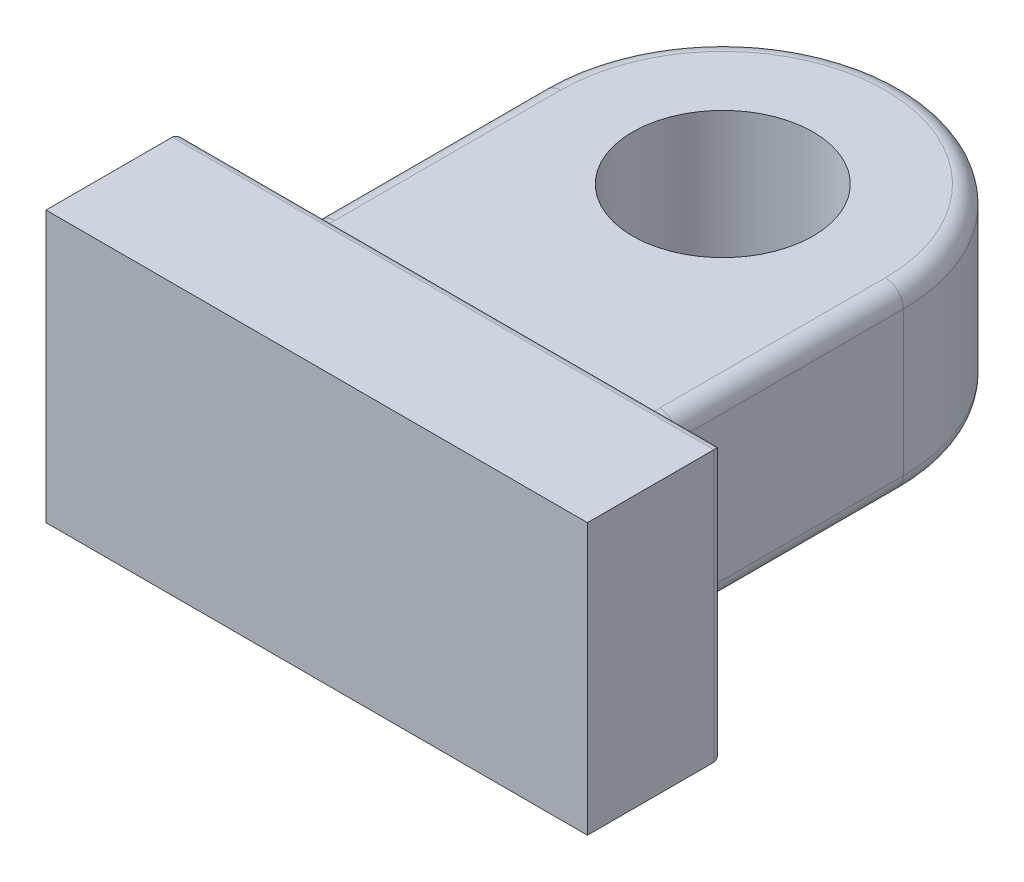
SolidWorks part; units mm, degrees
ref_plane "Front Plane" through (0, 0, 0) normal (0, 0, 1) x (1, 0, 0)
ref_plane "Top Plane" through (0, 0, 0) normal (0, 1, 0) x (1, 0, 0)
ref_plane "Right Plane" through (0, 0, 0) normal (1, 0, 0) x (0, 0, -1)
sketch "Sketch2" plane through (0, 0, 0) normal (0, 0, 1) x (1, 0, 0)
  line L1 (0, 0) -> (60, 0)
  line L2 (0, 0) -> (0, -30)
  line L3 (0, -30) -> (60, -30)
  line L4 (60, 0) -> (60, -30)
  dimension "D1" = 60
  dimension "D2" = 30
extrude "Boss-Extrude1" add sketch "Sketch2" along normal blind 15
ref_plane "Plane1" through (0, -15, 0) normal (0, 1, 0) x (1, 0, 0)
sketch "Sketch4" plane through (0, -15, 0) normal (0, 1, 0) x (1, 0, 0)
  line L0 (10, 30) -> (10, 0)
  line L1 (60, 0) -> (0, 0) construction
  line L2 (50, 30) -> (50, 0)
  line L3 (10, 0) -> (50, 0)
  circle A0 centre (30, 30) radius 10
  arc A1 (50, 30) -> (10, 30) centre (30, 30) ccw
  dimension "D1" = 20
  dimension "D2" = 20
  dimension "D3" = 30
  dimension "D4" = 10
extrude "Boss-Extrude2" add sketch "Sketch4" along normal mid plane 20
fillet "Fillet1" radius 5 2 edges at (10, -15, 0) (50, -15, 0)
fillet "Fillet2" radius 2 10 edges at (51.4645, -25, -1.4645) (50, -25, -17.5) (30, -25, -50) (8.5355, -25, -1.4645) (51.4645, -5, -1.4645) (50, -5, -17.5) (30, -5, -50) (8.5355, -5, -1.4645) (10, -25, -17.5) (10, -5, -17.5)
fillet "Fillet3" radius 1 10 edges at (30, -30, 0) (60, -15, 0) (30, 0, 0) (0, -15, 0) (51.6773, -5.266, 0) (51.6773, -24.734, 0) (30, -25, 0) (8.3227, -24.734, 0) (8.3227, -5.266, 0) (30, -5, 0)
sketch "Sketch5" plane through (0, 0, 15) normal (0, 0, 1) x (1, 0, 0)
  line L0 (30, 0) -> (30, -30) construction
  line L1 (60, 0) -> (0, 0) construction
  line L2 (0, -30) -> (60, -30) construction
